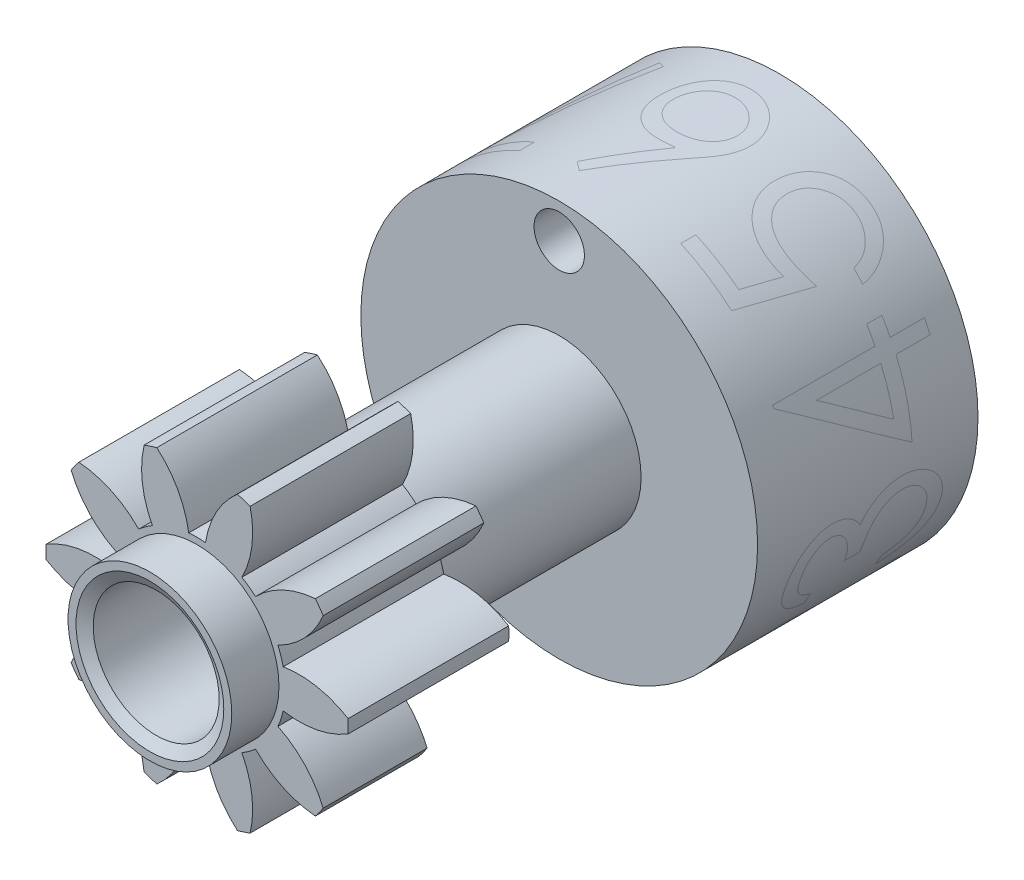
SolidWorks part; units mm, degrees
ref_plane "Front Plane" through (0, 0, 0) normal (0, 0, 1) x (1, 0, 0)
ref_plane "Top Plane" through (0, 0, 0) normal (0, 1, 0) x (1, 0, 0)
ref_plane "Right Plane" through (0, 0, 0) normal (1, 0, 0) x (0, 0, -1)
sketch "Sketch1" plane through (0, 0, 0) normal (0, 0, 1) x (1, 0, 0)
  circle A0 centre (0, 0) radius 1.3
  dimension "D1" = 2.6
extrude "Boss-Extrude1" add sketch "Sketch1" against normal blind 10
sketch "Sketch2" plane through (0, 0, -10) normal (0, 0, -1) x (-1, 0, 0)
  circle A0 centre (0, 0) radius 3.15
  dimension "D1" = 6.3
extrude "Boss-Extrude2" add sketch "Sketch2" against normal offset from surface (3.5 mm away) 6.5 up to face at (1.3, 0, 0)
sketch "Sketch3" plane through (0, 0, -10) normal (0, 0, -1) x (-1, 0, 0)
  circle A0 centre (0, 0) radius 1.75
  dimension "D1" = 3.5
extrude "Boss-Extrude3" add sketch "Sketch3" along normal offset from surface (0.2 mm away) 10.2 up to face at (1.3, 0, 0)
sketch "Sketch4" plane through (0, 0, 0) normal (1, 0, 0) x (0, 0, -1)
  line L0 (0, 0) -> (10.2, 0) construction
  line L1 (10.2, -1.75) -> (10.2, 1.75) construction
  line L2 (0, 1.3) -> (0, -1.3) construction
  line L4 (3.3, -1.3) -> (3.3, -2.4)
  line L7 (0, -1.3) -> (6.5, -1.3) construction
  line L9 (0.75, -1.3) -> (3.3, -1.3)
  line L10 (0.75, -1.3) -> (0.75, -2.4)
  line L11 (0.75, -2.4) -> (3.3, -2.4)
  dimension "D1" = 3.3
  dimension "D2" = 4.8
  dimension "D4" = 0.75
revolve "Revolve1" add sketch "Sketch4" angle 360 about L0
sketch "Sketch5" plane through (0, 0, 0) normal (0, 0, 1) x (1, 0, 0)
  circle A0 centre (0, 0) radius 1
  dimension "D1" = 2
extrude "Cut-Extrude1" cut sketch "Sketch5" against normal through all
chamfer "Chamfer1" distance 0.1 angle 45 1 edges at (1.75, 0, -10.2)
sketch "Sketch6" plane through (0, 0, 0) normal (1, 0, 0) x (0, 0, -1)
  line L0 (0, 0) -> (10.2, 0) construction
  line L1 (10.2, -1.65) -> (10.2, 1.65) construction
  line L2 (10.2, 1.4) -> (7.7751, 0)
  line L3 (7.7751, 0) -> (10.2, 0)
  line L4 (10.2, 0) -> (10.2, 1.4)
  dimension "D1" = 30
  dimension "D2" = 2.8
revolve "Cut-Revolve1" cut sketch "Sketch6" angle 360 about L0
chamfer "Chamfer2" distance 0.1 angle 60 1 edges at (1, 0, 0) first distance on face at (1, 0, 0)
sketch "Sketch7" plane through (0, 0, -6.5) normal (0, 0, 1) x (1, 0, 0)
  line L0 (0, 0) -> (0, 3.15) construction
  circle A0 centre (0, 2.6) radius 0.4
  circle A1 centre (0, 0) radius 3.15 construction
  dimension "D1" = 0.8
  dimension "D2" = 2.6
extrude "Cut-Extrude2" cut sketch "Sketch7" against normal up to next
sketch "Sketch8" plane through (0, 0, -0.75) normal (0, 0, 1) x (1, 0, 0)
  line L0 (0, 0) -> (0, 2.4) construction
  line L1 (0, 0) -> (-0.618, 1.9021) construction
  line L2 (0, 0) -> (0.618, 1.9021) construction
  line L3 (0, 0) -> (-2.4, 0) construction
  line L4 (0, 0) -> (-1.618, -1.1756) construction
  circle A0 centre (0, 0) radius 2.4 construction
  circle A1 centre (0, 0) radius 2 construction
  arc A2 (0.6402, -2.313) -> (0.134, -1.3936) centre (1.618, -1.1756) cw
  arc A3 (-0.134, -1.3936) -> (0.134, -1.3936) centre (0, 0) ccw
  arc A4 (-0.6402, -2.313) -> (-0.134, -1.3936) centre (-1.618, -1.1756) ccw
  arc A5 (-0.6402, -2.313) -> (0.6402, -2.313) centre (0, 0) ccw
  dimension "D1" = 4
  dimension "D4" = 2.8
  dimension "D6" = 3
  dimension "D2" = 18
  dimension "D3" = 18
  dimension "D5" = 36
extrude "Cut-Extrude3" cut sketch "Sketch8" against normal up to next
pattern_circular "CirPattern1" count 10 over 360 about axis through (0, 0, -10.2) along (0, 0, 1) of "Cut-Extrude3"
sketch "Sketch10" plane through (0, 0, -0.75) normal (0, 0, 1) x (1, 0, 0)
  line L0 (0, 0) -> (1.6068, 2.2116) construction
  circle A0 centre (0, 0) radius 1.9874 construction
  circle A1 centre (1.6068, 2.2116) radius 0.7463
  arc A2 (0.7107, 1.2062) -> (0.8416, 2.2476) centre (-0.618, 1.9021) ccw construction
  arc A3 (1.8775, 1.495) -> (0.9275, 1.0487) centre (2, 0) ccw construction
  dimension "D1" = 3.48
sketch "Sketch11" plane through (0, 0, -3.3) normal (0, 0, -1) x (-1, 0, 0)
  line L0 (0, 0) -> (-4.5553, -6.2698) construction
  line L1 (0, 0) -> (-3.15, 0) construction
  circle A0 centre (0, 0) radius 3.15 construction
  circle A1 centre (-3.703, -5.0968) radius 5
  point P9 (-0.7641, -1.0517)
  dimension "D2" = 10
  dimension "D1" = 54
  dimension "D3" = 1.3
extrude "Cut-Extrude4" cut sketch "Sketch11" against normal offset from surface (0.9 mm away) 2.4 contours A1 up to face at (1.1732, 0, 0)
sketch "Sketch12" plane through (0, 0, -10) normal (0, 0, -1) x (-1, 0, 0)
  line L0 (0, 0) -> (0, 3.15) construction
  line L1 (0, 0) -> (1.8515, 2.5484) construction
  line L2 (0, 0) -> (2.9958, 0.9734) construction
  line L3 (0, 0) -> (2.9958, -0.9734) construction
  line L4 (0, 0) -> (1.8515, -2.5484) construction
  line L5 (0, 0) -> (0, -3.15) construction
  line L6 (0, 0) -> (-1.8515, -2.5484) construction
  line L7 (0, 0) -> (-2.9958, -0.9734) construction
  line L8 (0, 0) -> (-2.9958, 0.9734) construction
  line L9 (0, 0) -> (-1.8515, 2.5484) construction
  circle A0 centre (0, 0) radius 3.15 construction
  point P17 (0, 0)
  dimension "D1" = 10
ref_plane "Plane2" through (0, 3.15, -10) normal (0, 1, 0) x (1, 0, 0)
sketch "Sketch14" plane through (0, 3.15, -10) normal (0, 1, 0) x (1, 0, 0)
  line L0 (0, 0) -> (0, -3.5) construction
  line L1 (-0.675, -0.5) -> (0.675, -0.5)
  line L2 (-0.675, -0.5) -> (-0.675, -2.85)
  line L3 (-0.675, -2.85) -> (0.675, -2.85)
  line L4 (0.675, -0.5) -> (0.675, -2.85)
  line L5 (-3.15, -3.5) -> (3.15, -3.5) construction
  line L6 (0, 0) -> (1.8515, 0) construction
  line L7 (-2.5, -0.5) -> (2.5, -0.5)
  dimension "D1" = 0.5
  dimension "D2" = 2.35
  dimension "D3" = 1.35
  dimension "D4" = 5
sketch "Sketch20" plane through (0, 3.15, -10) normal (0, 1, 0) x (1, 0, 0)
  text T0 "6" font "Century Gothic" height 2.35
wrap "Wrap2" sketch "Sketch20" wrap type scribe source sketch "Sketch20" face at (-3.15, 0, -10)
ref_plane "Plane3" through (1.8515, 2.5484, -10) normal (0.5878, 0.809, 0) x (0.809, -0.5878, 0)
sketch "Sketch21" plane through (1.8515, 2.5484, -10) normal (0.5878, 0.809, 0) x (0.809, -0.5878, 0)
  line L0 (0, 0) -> (0, -3.5) construction
  line L1 (-1.3, -3.5) -> (1.3, -3.5) construction
  line L3 (-1, -0.5) -> (1, -0.5) construction
  line L4 (0, 0) -> (1.8515, 0) construction
  text T0 "5" font "Century Gothic" height 2.35
  dimension "D1" = 2
  dimension "D2" = 0.5
wrap "Wrap3" sketch "Sketch21" wrap type scribe source sketch "Sketch21" face at (-3.15, 0, -10)
ref_plane "Plane4" through (2.9958, 0.9734, -10) normal (0.9511, 0.309, 0) x (0, 0, -1)
sketch "Sketch22" plane through (2.9958, 0.9734, -10) normal (0.9511, 0.309, 0) x (0, 0, -1)
  line L0 (0, 0) -> (-3.5, 0) construction
  line L1 (-3.5, 3.15) -> (-3.5, -3.15) construction
  line L2 (-0.5, 1) -> (-0.5, -1) construction
  line L3 (0, 0) -> (0, -1.8515) construction
  text T0 "4" font "Century Gothic" height 2.35
  dimension "D1" = 2
  dimension "D2" = 0.5
wrap "Wrap4" sketch "Sketch22" wrap type scribe source sketch "Sketch22" face at (1.8301, 2.528, -8.2739)
ref_plane "Plane5" through (2.9958, -0.9734, -10) normal (0.9511, -0.309, 0) x (0, 0, -1)
sketch "Sketch24" plane through (2.9958, -0.9734, -10) normal (0.9511, -0.309, 0) x (0, 0, -1)
  line L0 (0, 0) -> (-3.5, 0) construction
  line L1 (-3.5, 3.15) -> (-3.5, -3.15) construction
  line L2 (-0.5, 1) -> (-0.5, -1) construction
  line L3 (0, 0) -> (0, -1.8515) construction
  text T0 "3" font "Century Gothic" height 2.35
  dimension "D1" = 0.5
  dimension "D2" = 2
wrap "Wrap5" sketch "Sketch24" wrap type scribe source sketch "Sketch24" face at (1.8301, 2.528, -8.2739)
ref_plane "Plane6" through (1.8515, -2.5484, -10) normal (0.5878, -0.809, 0) x (-0.809, -0.5878, 0)
sketch "Sketch25" plane through (1.8515, -2.5484, -10) normal (0.5878, -0.809, 0) x (-0.809, -0.5878, 0)
  line L0 (0, 0) -> (0, -3.5) construction
  line L1 (-3.15, -3.5) -> (3.15, -3.5) construction
  line L2 (-1, -0.5) -> (1, -0.5) construction
  line L3 (0, 0) -> (1.8515, 0) construction
  text T0 "2" font "Century Gothic" height 2.35
  point P8 (0, -0.5)
  dimension "D1" = 2
  dimension "D2" = 0.5
wrap "Wrap6" sketch "Sketch25" wrap type scribe source sketch "Sketch25" face at (1.8301, 2.528, -8.2739)
ref_plane "Plane7" through (0, -3.15, -10) normal (0, -1, 0) x (-1, 0, 0)
sketch "Sketch26" plane through (0, -3.15, -10) normal (0, -1, 0) x (-1, 0, 0)
  line L0 (0, 0) -> (0, -3.5) construction
  line L1 (-3.15, -3.5) -> (3.15, -3.5) construction
  line L2 (-1, -0.5) -> (1, -0.5) construction
  line L3 (0, 0) -> (1.8515, 0) construction
  text T0 "1" font "Century Gothic" height 2.35
  point P8 (0, -0.5)
  dimension "D1" = 2
  dimension "D2" = 0.5
wrap "Wrap7" sketch "Sketch26" wrap type scribe source sketch "Sketch26" face at (1.8301, 2.528, -8.2739)
ref_plane "Plane8" through (-1.8515, -2.5484, -10) normal (-0.5878, -0.809, 0) x (-0.809, 0.5878, 0)
sketch "Sketch27" plane through (-1.8515, -2.5484, -10) normal (-0.5878, -0.809, 0) x (-0.809, 0.5878, 0)
  line L0 (0, 0) -> (0, -3.5) construction
  line L1 (-3.15, -3.5) -> (3.15, -3.5) construction
  line L2 (-1, -0.5) -> (1, -0.5) construction
  line L3 (0, 0) -> (1.8515, 0) construction
  text T0 "0" font "Century Gothic" height 2.35
  point P8 (0, -0.5)
  dimension "D1" = 0.5
  dimension "D2" = 2
wrap "Wrap8" sketch "Sketch27" wrap type scribe source sketch "Sketch27" face at (1.8301, 2.528, -8.2739)
ref_plane "Plane9" through (-2.9958, -0.9734, -10) normal (-0.9511, -0.309, 0) x (0, 0, 1)
sketch "Sketch28" plane through (-2.9958, -0.9734, -10) normal (-0.9511, -0.309, 0) x (0, 0, 1)
  line L0 (0, 0) -> (3.5, 0) construction
  line L1 (3.5, -3.15) -> (3.5, 3.15) construction
  line L2 (0.5, -1) -> (0.5, 1) construction
  line L3 (0, 0) -> (0, 1.8515) construction
  text T0 "9" font "Century Gothic" height 2.35
  point P8 (0.5, 0)
  dimension "D1" = 2
  dimension "D2" = 0.5
wrap "Wrap9" sketch "Sketch28" wrap type scribe source sketch "Sketch28" face at (-1.8048, -2.5201, -8.3255)
ref_plane "Plane10" through (-2.9958, 0.9734, -10) normal (-0.9511, 0.309, 0) x (0, 0, 1)
sketch "Sketch29" plane through (-2.9958, 0.9734, -10) normal (-0.9511, 0.309, 0) x (0, 0, 1)
  line L0 (0, 0) -> (3.5, 0) construction
  line L1 (3.5, -3.15) -> (3.5, 3.15) construction
  line L2 (0.5, -1) -> (0.5, 1) construction
  line L3 (0, 0) -> (0, -1.8515) construction
  text T0 "8" font "Century Gothic" height 2.35
  point P8 (0.5, 0)
  dimension "D1" = 0.5
  dimension "D2" = 2
wrap "Wrap10" sketch "Sketch29" wrap type scribe source sketch "Sketch29" face at (-1.8048, -2.5201, -8.3255)
ref_plane "Plane11" through (-1.8515, 2.5484, -10) normal (-0.5878, 0.809, 0) x (0.809, 0.5878, 0)
sketch "Sketch30" plane through (-1.8515, 2.5484, -10) normal (-0.5878, 0.809, 0) x (0.809, 0.5878, 0)
  line L0 (0, 0) -> (0, -3.5) construction
  line L1 (-3.15, -3.5) -> (3.15, -3.5) construction
  line L2 (-1, -0.5) -> (1, -0.5) construction
  line L4 (0, 0) -> (2.9958, 0) construction
  text T0 "7" font "Century Gothic" height 2.35
  point P9 (0, -0.5)
  dimension "D1" = 2
  dimension "D2" = 0.5
wrap "Wrap11" sketch "Sketch30" wrap type scribe source sketch "Sketch30" face at (-1.8048, -2.5201, -8.3255)
